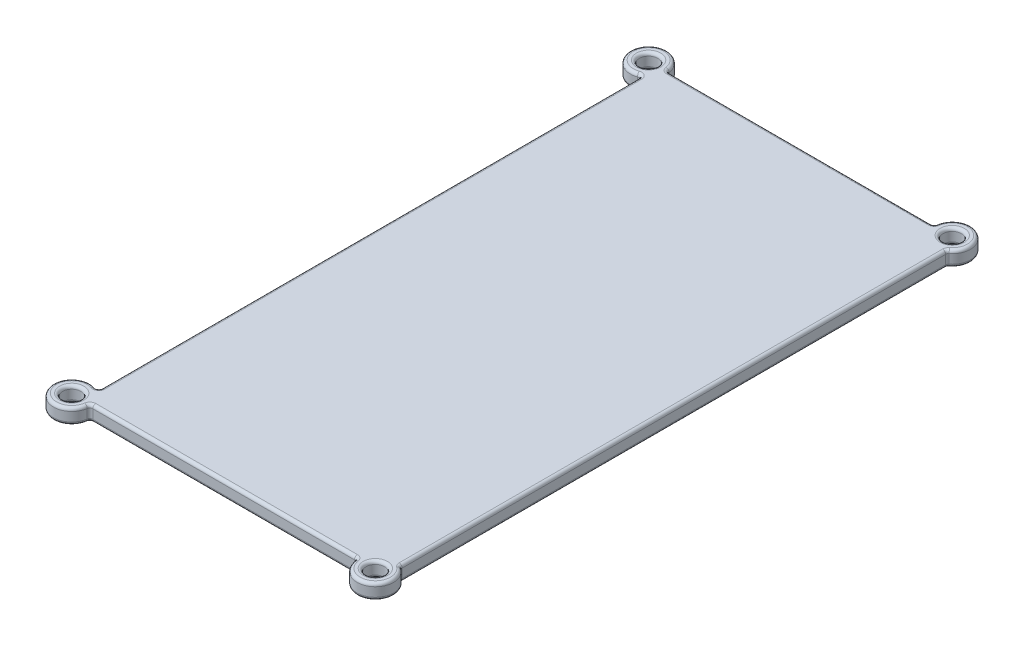
SolidWorks part; units mm, degrees
ref_plane "Front Plane" through (0, 0, 0) normal (0, 0, 1) x (1, 0, 0)
ref_plane "Top Plane" through (0, 0, 0) normal (0, 1, 0) x (1, 0, 0)
ref_plane "Right Plane" through (0, 0, 0) normal (1, 0, 0) x (0, 0, -1)
sketch "Sketch4" plane through (0, 0, 0) normal (0, 1, 0) x (1, 0, 0)
  line L0 (0, 50) -> (0, -50) construction
  line L1 (-22, 47.5) -> (22, 47.5)
  line L2 (-23.3417, 45) -> (-23.3417, -45)
  line L3 (-22, -47.5) -> (22, -47.5)
  line L4 (26.6583, 45) -> (26.6583, -45)
  line L5 (-25, 47.5) -> (25, -47.5) construction
  line L6 (-25, -47.5) -> (25, 47.5) construction
  line L7 (-24, 0) -> (24, 0) construction
  arc A0 (-22, 47.5) -> (-23.3417, 45) centre (-25, 47.5) ccw
  arc A1 (22, 47.5) -> (26.6583, 45) centre (25, 47.5) cw
  arc A2 (-22, -47.5) -> (-23.3417, -45) centre (-25, -47.5) cw
  arc A3 (22, -47.5) -> (26.6583, -45) centre (25, -47.5) ccw
  circle A4 centre (-25, 47.5) radius 1.5
  circle A5 centre (25, 47.5) radius 1.5
  circle A6 centre (25, -47.5) radius 1.5
  circle A7 centre (-25, -47.5) radius 1.5
  point P0 (0, 0)
  dimension "D3" = 6
  dimension "D4" = 3
  dimension "D5" = 90
  dimension "D6" = 44
  dimension "D1" = 95
  dimension "D2" = 50
extrude "Boss-Extrude3" add sketch "Sketch4" along normal blind 2.5
fillet "Fillet1" radius 0.5 32 edges at (26.6583, 1.25, -45) (22, 1.25, -47.5) (-22, 1.25, -47.5) (26.6583, 1.25, 45) (22, 1.25, 47.5) (-22, 1.25, 47.5) (-23.3417, 1.25, -45) (-23.3417, 1.25, 45) (-25, 0, 46) (25, 0, 49) (25, 0, -49) (-25, 0, -46) (-23.3417, 0, 0) (-27.6434, 0, 48.9186) (0, 0, 47.5) (26.4186, 0, 50.1434) (26.6583, 0, 0) (26.4186, 0, -50.1434) (0, 0, -47.5) (-27.6434, 0, -48.9186) (-25, 2.5, 46) (25, 2.5, -49) (0, 2.5, -47.5) (26.4186, 2.5, -50.1434) (26.6583, 2.5, 0) (26.4186, 2.5, 50.1434) (0, 2.5, 47.5) (-27.6434, 2.5, 48.9186) (-23.3417, 2.5, 0) (-27.6434, 2.5, -48.9186) (-25, 2.5, -46) (25, 2.5, 49)
